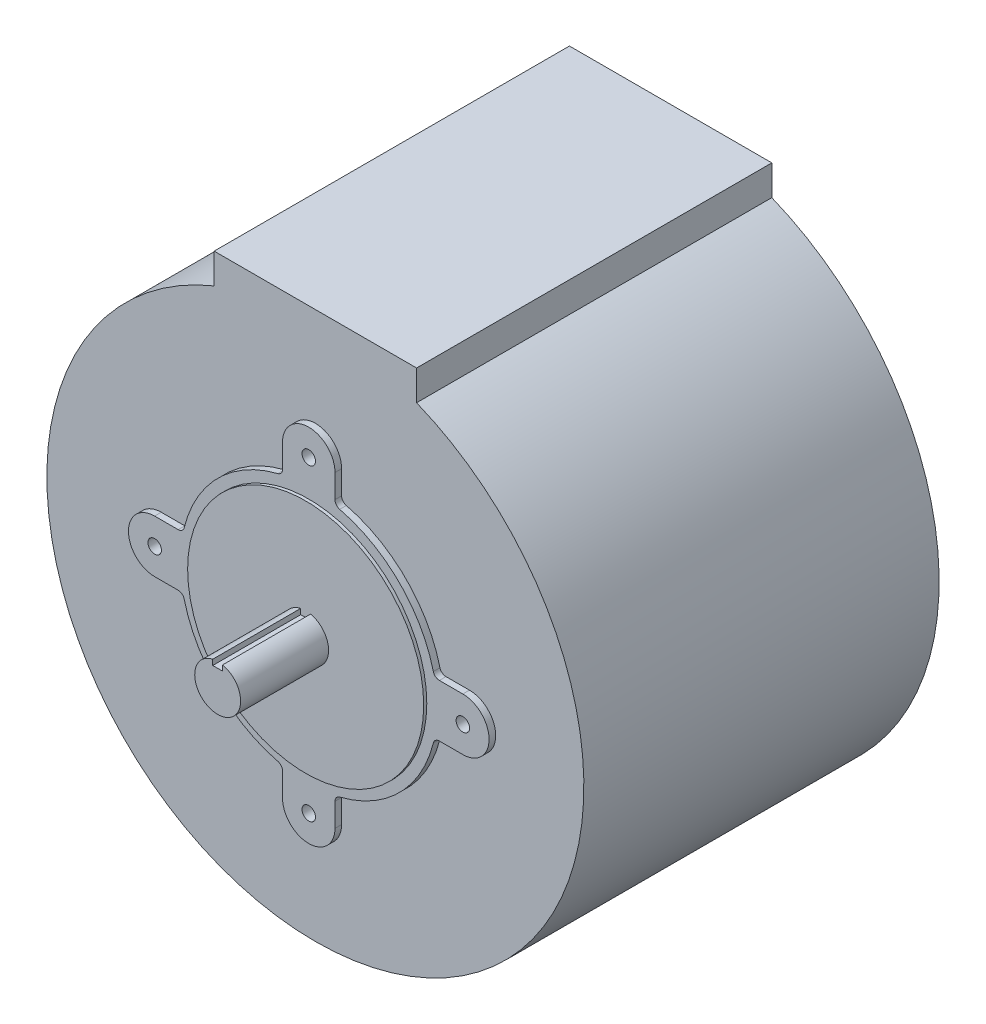
SolidWorks part; units mm, degrees
ref_plane "Front Plane" through (0, 0, 0) normal (0, 0, 1) x (1, 0, 0)
ref_plane "Top Plane" through (0, 0, 0) normal (0, 1, 0) x (1, 0, 0)
ref_plane "Right Plane" through (0, 0, 0) normal (1, 0, 0) x (0, 0, -1)
sketch "Sketch1" plane through (0, 0, 0) normal (0, 0, 1) x (1, 0, 0)
  circle A0 centre (0, 0) radius 130
  dimension "D1" = 260
extrude "Boss-Extrude1" add sketch "Sketch1" against normal blind 172
sketch "Sketch2" plane through (0, 0, 0) normal (0, 0, 1) x (1, 0, 0)
  line L0 (-74.6, 12.7) -> (-63.23, 12.7)
  line L1 (-74.6, -12.7) -> (-63.23, -12.7)
  line L2 (-12.7, -74.6) -> (-12.7, -63.23)
  line L3 (12.7, -74.6) -> (12.7, -63.23)
  line L4 (74.6, -12.7) -> (63.23, -12.7)
  line L5 (74.6, 12.7) -> (63.23, 12.7)
  line L6 (12.7, 74.6) -> (12.7, 63.23)
  line L7 (-12.7, 74.6) -> (-12.7, 63.23)
  circle A0 centre (0, 0) radius 74.6 construction
  arc A1 (12.6539, 73.519) -> (-12.6539, 73.519) centre (0, 74.6) ccw
  arc A2 (73.519, -12.6539) -> (73.519, 12.6539) centre (74.6, 0) ccw
  arc A3 (-12.6539, -73.519) -> (12.6539, -73.519) centre (0, -74.6) ccw
  arc A4 (-73.519, 12.6539) -> (-73.519, -12.6539) centre (-74.6, 0) ccw
  arc A5 (-14.9771, 60.3184) -> (-60.3184, 14.9771) centre (0, 0) ccw
  arc A6 (-60.3184, -14.9771) -> (-14.9771, -60.3184) centre (0, 0) ccw
  arc A7 (14.9771, -60.3184) -> (60.3184, -14.9771) centre (0, 0) ccw
  arc A8 (60.3184, 14.9771) -> (14.9771, 60.3184) centre (0, 0) ccw
  arc A9 (12.7, 63.23) -> (14.9771, 60.3184) centre (15.7, 63.23) ccw
  arc A10 (63.23, 12.7) -> (60.3184, 14.9771) centre (63.23, 15.7) cw
  arc A11 (63.23, -12.7) -> (60.3184, -14.9771) centre (63.23, -15.7) ccw
  arc A12 (12.7, -63.23) -> (14.9771, -60.3184) centre (15.7, -63.23) cw
  arc A13 (-12.7, -63.23) -> (-14.9771, -60.3184) centre (-15.7, -63.23) ccw
  arc A14 (-63.23, -12.7) -> (-60.3184, -14.9771) centre (-63.23, -15.7) cw
  arc A15 (-63.23, 12.7) -> (-60.3184, 14.9771) centre (-63.23, 15.7) ccw
  arc A16 (-12.7, 63.23) -> (-14.9771, 60.3184) centre (-15.7, 63.23) cw
  point P35 (60.8386, 12.7)
  point P38 (60.8386, -12.7)
  point P41 (12.7, -60.8386)
  point P44 (-12.7, -60.8386)
  point P47 (-60.8386, -12.7)
  dimension "D1" = 149.2
  dimension "D2" = 124.3
  dimension "D3" = 25.4
  dimension "D4" = 3
extrude "Boss-Extrude2" add sketch "Sketch2" along normal blind 3.2 contours L7 A16 A5 A15 L0 A4 L1 A14 A6 A13 L2 A3 L3 A12 A7 A11 L4 A2 L5 A10 A8 A9 L6 A1 region at (0, 0, 0)
sketch "Sketch3" plane through (0, 0, 3.2) normal (0, 0, 1) x (1, 0, 0)
  circle A0 centre (0, 0) radius 57.15
  dimension "D1" = 114.3
extrude "Boss-Extrude3" add sketch "Sketch3" along normal blind 1.5
hole_wizard "5/16-18 Tapped Hole1" positions "Sketch5" profile "Sketch4" tap size "5/16-18" standard "ANSI Inch"
sketch "Sketch5" plane through (0, 0, 3.2) normal (0, 0, 1) x (1, 0, 0)
  circle A0 centre (0, 0) radius 74.6 construction
  point P0 (-74.6, 0)
  point P4 (0, 74.6)
  point P12 (74.6, 0)
  point P14 (0, -74.6)
sketch "Sketch4" plane through (-74.6, 0, 3.2) normal (1, 0, 0) x (0, -1, 0)
  line L0 (0, 0) -> (0, 22.0702)
  line L1 (0, 22.0702) -> (3.2639, 20.1091)
  line L2 (3.2639, 20.1091) -> (3.2639, 0)
  line L5 (3.2639, 0) -> (0, 0)
  line L10 (0, 22.0702) -> (-3.2639, 20.1091) construction
  line L11 (0, -6.35) -> (0, 107.95) construction
  dimension "Tap Drill Dia." = 6.5278
  dimension "Tap Drill Depth" = 20.1091
  dimension "Drill Angle" = 118
cosmetic thread "Hole Thread1" parameters "D1"=15.88, "D2"=7.9375
cosmetic thread "Hole Thread2" parameters "D1"=15.88, "D2"=7.9375
cosmetic thread "Hole Thread3" parameters "D1"=15.88, "D2"=7.9375
cosmetic thread "Hole Thread4" parameters "D1"=15.88, "D2"=7.9375
sketch "Sketch6" plane through (0, 0, 0) normal (0, 0, 1) x (1, 0, 0)
  line L1 (-49, 135) -> (49, 135)
  line L2 (-49, 135) -> (-49, 87.3)
  line L3 (-49, 87.3) -> (49, 87.3)
  line L4 (49, 135) -> (49, 87.3)
  line L5 (-49, 135) -> (49, 87.3) construction
  line L6 (-49, 87.3) -> (49, 135) construction
  circle A0 centre (0, 0) radius 130 construction
  arc A1 (12.6539, 73.519) -> (-12.6539, 73.519) centre (0, 74.6) ccw construction
  point P0 (0, 130)
  point P7 (0, 87.3)
  dimension "D1" = 135
  dimension "D2" = 98
extrude "Boss-Extrude4" add sketch "Sketch6" against normal up to surface (172 mm away) up to face at (130, 0, -172)
sketch "Sketch7" plane through (0, 0, 4.7) normal (0, 0, 1) x (1, 0, 0)
  line L2 (-2.39, 10.855) -> (-2.39, 8.205)
  line L3 (-2.39, 8.205) -> (2.39, 8.205)
  line L4 (2.39, 10.855) -> (2.39, 8.205)
  arc A0 (-2.39, 10.855) -> (2.39, 10.855) centre (0, 0) ccw
  point P7 (0, 8.205)
  dimension "D1" = 22.23
  dimension "D2" = 2.65
  dimension "D3" = 4.78
extrude "Boss-Extrude5" add sketch "Sketch7" along normal blind 42.6
